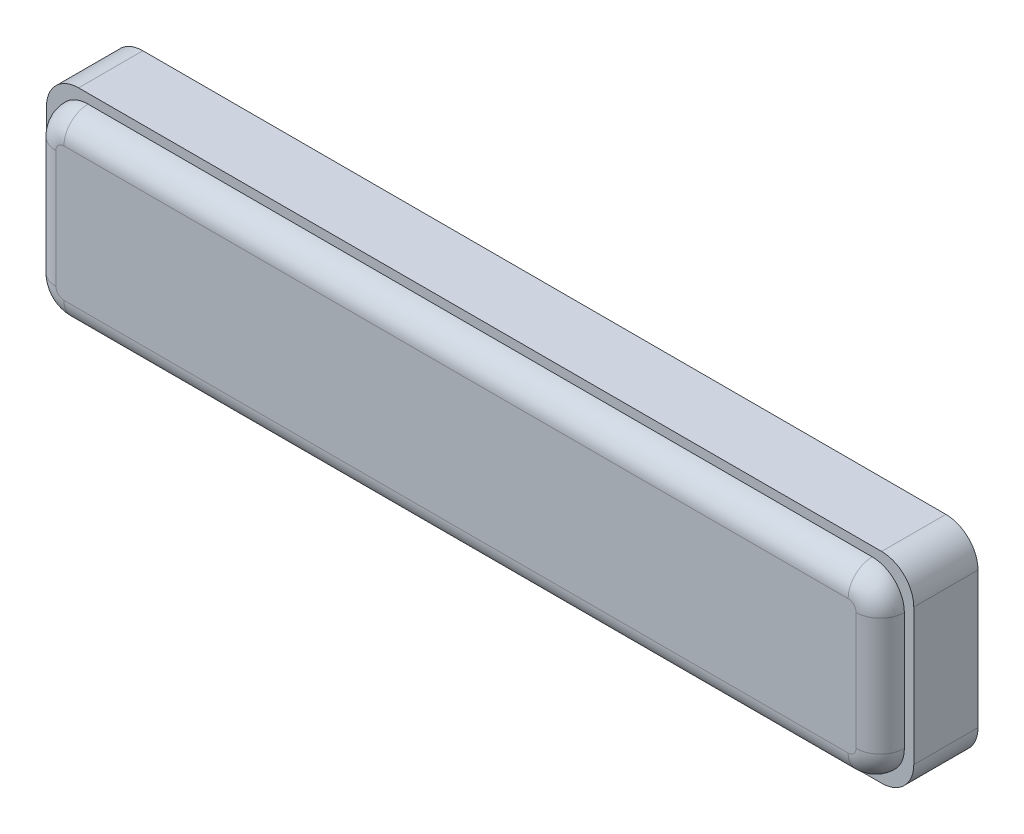
SolidWorks part; units mm, degrees
ref_plane "정면" through (0, 0, 0) normal (0, 0, 1) x (1, 0, 0)
ref_plane "윗면" through (0, 0, 0) normal (0, 1, 0) x (1, 0, 0)
ref_plane "우측면" through (0, 0, 0) normal (1, 0, 0) x (0, 0, -1)
sketch "스케치1" plane through (0, 0, 0) normal (0, 0, 1) x (1, 0, 0)
  line L1 (-78.0969, 13.3409) -> (21.9031, 13.3409)
  line L2 (-82.0969, 9.3409) -> (-82.0969, -7.6591)
  line L3 (-78.0969, -11.6591) -> (21.9031, -11.6591)
  line L4 (25.9031, 9.3409) -> (25.9031, -7.6591)
  line L5 (-82.0969, 13.3409) -> (25.9031, -11.6591) construction
  line L6 (-82.0969, -11.6591) -> (25.9031, 13.3409) construction
  arc A0 (21.9031, 13.3409) -> (25.9031, 9.3409) centre (21.9031, 9.3409) cw
  arc A1 (21.9031, -11.6591) -> (25.9031, -7.6591) centre (21.9031, -7.6591) ccw
  arc A2 (-82.0969, -7.6591) -> (-78.0969, -11.6591) centre (-78.0969, -7.6591) ccw
  arc A3 (-78.0969, 13.3409) -> (-82.0969, 9.3409) centre (-78.0969, 9.3409) ccw
  point P0 (-28.0969, 0.8409)
  dimension "D3" = 4
  dimension "D1" = 108
  dimension "D2" = 25
extrude "보스-돌출1" add sketch "스케치1" along normal blind 8
sketch "스케치2" plane through (0, 0, 0) normal (0, 0, -1) x (-1, 0, 0)
  line L0 (4.2352, 8.3409) -> (70.2717, 8.3409)
  line L1 (-20.7315, 12.1693) -> (76.9253, 12.1693)
  line L2 (-24.7315, 8.1693) -> (-24.7315, -6.4875)
  line L3 (-20.7315, -10.4875) -> (76.9253, -10.4875)
  line L4 (80.9253, 8.1693) -> (80.9253, -6.4875)
  line L5 (-24.7315, 12.1693) -> (10.0711, 4.7063) construction
  line L6 (-24.7315, -10.4875) -> (10.7473, -2.8795) construction
  line L7 (4.2352, -6.6591) -> (70.2717, -6.6591)
  line L8 (28.0969, 0.8409) -> (80.9253, -10.4875) construction
  line L9 (28.0969, 0.8409) -> (80.9253, 12.1693) construction
  arc A0 (78.0969, -11.6591) -> (82.0969, -7.6591) centre (78.0969, -7.6591) ccw construction
  arc A1 (-21.9031, 13.3409) -> (-25.9031, 9.3409) centre (-21.9031, 9.3409) ccw construction
  arc A2 (76.9253, -10.4875) -> (80.9253, -6.4875) centre (76.9253, -6.4875) ccw
  arc A3 (76.9253, 12.1693) -> (80.9253, 8.1693) centre (76.9253, 8.1693) cw
  arc A4 (-24.7315, -6.4875) -> (-20.7315, -10.4875) centre (-20.7315, -6.4875) ccw
  arc A5 (-20.7315, 12.1693) -> (-24.7315, 8.1693) centre (-20.7315, 8.1693) ccw
  arc A6 (70.2717, -6.6591) -> (70.2717, 8.3409) centre (70.2717, 0.8409) ccw
  arc A7 (4.2352, 8.3409) -> (4.2352, -6.6591) centre (4.2352, 0.8409) ccw
  circle A8 centre (4.2352, 0.8409) radius 7
  circle A9 centre (70.2717, 0.8409) radius 7
  circle A10 centre (4.2352, 0.8409) radius 3
  circle A11 centre (70.2717, 0.8409) radius 3
  circle A12 centre (4.2352, 0.8409) radius 0.7209
  circle A13 centre (70.2717, 0.8409) radius 0.8409
  point P0 (28.0969, 0.8409)
  point P26 (0, 0)
  dimension "D1" = 4
  dimension "D2" = 15
  dimension "D3" = 15
  dimension "D4" = 6
  dimension "D5" = 6
  dimension "D6" = 14
  dimension "D7" = 14
extrude "컷-돌출1" cut sketch "스케치2" against normal blind 2 contours L1 A5 L2 A4 L3 A2 L4 A3 A7 L0 A6 L7 | A8 A10 | A9 A11 | A13 | A12 region at (-28.0969, 11.0887, 0) region at (2.5668, 0.8409, 0) region at (-63.4697, 0.8409, 0) region at (-70.2717, 0.8409, 0)
sketch "스케치3" plane through (0, 0, 8) normal (0, 0, 1) x (1, 0, 0)
  line L1 (-76.9253, 12.1693) -> (20.7315, 12.1693)
  line L2 (-80.9253, 8.1693) -> (-80.9253, -6.4875)
  line L3 (-76.9253, -10.4875) -> (20.7315, -10.4875)
  line L4 (24.7315, 8.1693) -> (24.7315, -6.4875)
  arc A0 (-78.0969, 13.3409) -> (-82.0969, 9.3409) centre (-78.0969, 9.3409) ccw construction
  arc A1 (21.9031, -11.6591) -> (25.9031, -7.6591) centre (21.9031, -7.6591) ccw construction
  arc A2 (20.7315, -10.4875) -> (24.7315, -6.4875) centre (20.7315, -6.4875) ccw
  arc A3 (20.7315, 12.1693) -> (24.7315, 8.1693) centre (20.7315, 8.1693) cw
  arc A4 (-80.9253, -6.4875) -> (-76.9253, -10.4875) centre (-76.9253, -6.4875) ccw
  arc A5 (-76.9253, 12.1693) -> (-80.9253, 8.1693) centre (-76.9253, 8.1693) ccw
  point P12 (24.7315, -10.4875)
  point P19 (-80.9253, 12.1693)
  dimension "D1" = 4
extrude "보스-돌출2" add sketch "스케치3" along normal blind 3
fillet "필렛1" radius 3 8 edges at (-28.0969, -10.4875, 11) (-79.7538, -9.3159, 11) (-80.9253, 0.8409, 11) (-79.7538, 10.9978, 11) (-28.0969, 12.1693, 11) (23.5599, 10.9978, 11) (24.7315, 0.8409, 11) (23.5599, -9.3159, 11)
